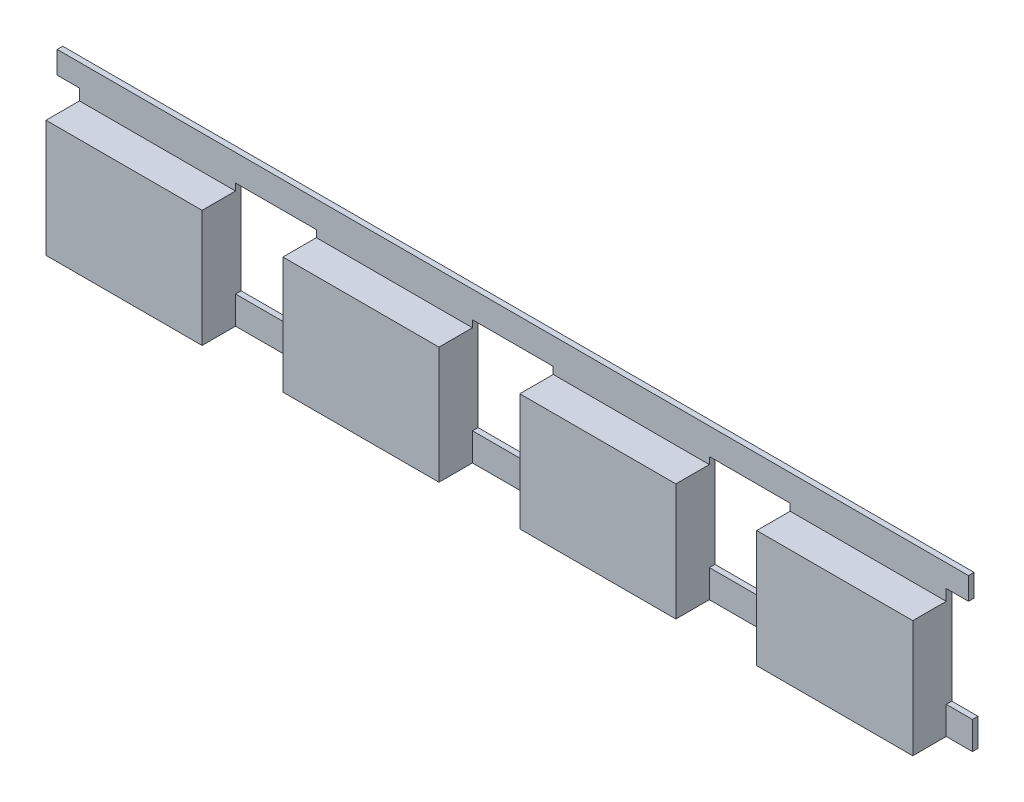
SolidWorks part; units mm, degrees
ref_plane "Спереди" through (0, 0, 0) normal (0, 0, 1) x (1, 0, 0)
ref_plane "Сверху" through (0, 0, 0) normal (0, 1, 0) x (1, 0, 0)
ref_plane "Справа" through (0, 0, 0) normal (1, 0, 0) x (0, 0, -1)
other "Configuration Table"
sketch "Эскиз1" plane through (0, 0, 0) normal (0, 0, 1) x (1, 0, 0)
  line L1 (-2.8, -2.1) -> (2.8, -2.1)
  line L2 (-2.8, -2.1) -> (-2.8, 2.1)
  line L3 (-2.8, 2.1) -> (2.8, 2.1)
  line L4 (2.8, -2.1) -> (2.8, 2.1)
  line L5 (-2.8, -2.1) -> (2.8, 2.1) construction
  line L6 (-2.8, 2.1) -> (2.8, -2.1) construction
  point P0 (0, 0)
  dimension "D1" = 4.2
  dimension "D2" = 5.6
extrude "Бобышка-Вытянуть1" add sketch "Эскиз1" along normal blind 1.4
sketch "Эскиз2" plane through (0, 0, 1.4) normal (0, 0, 1) x (1, 0, 0)
  line L0 (0, 0) -> (-1.0279, 0)
sketch "Эскиз3" plane through (0, 0, 0) normal (0, 0, -1) x (-1, 0, 0)
  line L1 (2.8, 2.1) -> (-28.3, 2.1)
  line L2 (2.8, 2.1) -> (2.8, 3.3)
  line L3 (2.8, 3.3) -> (-28.3, 3.3)
  line L4 (-28.3, 2.1) -> (-28.3, 3.3)
  line L5 (2.8, 2.1) -> (-28.3, 2.1)
  line L6 (2.8, 2.1) -> (2.8, 1.8)
  line L7 (2.8, 1.8) -> (-28.3, 1.8)
  line L8 (-28.3, 2.1) -> (-28.3, 1.8)
  line M5 (-2.8, 2.1) -> (-2.8, -2.1)
  line M7 (2.8, -2.1) -> (2.8, 2.1)
  line M8 (2.8, 2.1) -> (-2.8, 2.1)
  dimension "D1" = 1.2
  dimension "D2" = 0.3
  dimension "D3" = 31.1
  dimension "D4" = 31.1
extrude "Бобышка-Вытянуть2" add sketch "Эскиз3" against normal blind 0.2 contours L4 L1 L2 L3 M8 | L1 L8 L7 M5 | L7 M7 M8 M5 region at (0, 1.95, 0) region at (12.75, 2.7, 0) region at (15.55, 1.95, 0)
pattern_linear "Линейный массив1" count 4 spacing 8.5 along (1, 0, 0) of "Бобышка-Вытянуть1"
sketch "Эскиз4" plane through (0, 0, 0) normal (0, 0, -1) x (-1, 0, 0)
  line L0 (-22.7, 1.8) -> (-19.8, 1.8)
  line L2 (-22.7, 2.35) -> (-19.8, 2.35)
  line L3 (-22.7, 2.35) -> (-22.7, 1.25)
  line L4 (-22.7, 1.25) -> (-19.8, 1.25)
  line L5 (-19.8, 2.35) -> (-19.8, 1.25)
  line L6 (-22.7, 2.35) -> (-19.8, 1.25) construction
  line L7 (-22.7, 1.25) -> (-19.8, 2.35) construction
  line L8 (-14.2, 2.35) -> (-14.2, 1.25)
  line L9 (-14.2, 2.35) -> (-11.3, 2.35)
  line L10 (-11.3, 2.35) -> (-11.3, 1.25)
  line L11 (-14.2, 1.25) -> (-11.3, 1.25)
  line L12 (-5.7, 2.35) -> (-5.7, 1.25)
  line L13 (-5.7, 2.35) -> (-2.8, 2.35)
  line L14 (-2.8, 2.35) -> (-2.8, 1.25)
  line L15 (-5.7, 1.25) -> (-2.8, 1.25)
  point P4 (-21.25, 1.8)
  dimension "D1" = 1.1
  dimension "D2" = 3
extrude "Вырез-Вытянуть1" cut sketch "Эскиз4" against normal blind 0.2 contours L12 L15 L14 L13 | L8 L11 L10 L9 | L5 L0 L4 | L5 L2 L3 L0 region at (21.25, 2.075, 0) region at (21.25, 1.525, 0) region at (12.75, 1.8, 0) region at (4.25, 1.8, 0)
sketch "Эскиз5" plane through (28.3, 0, 0) normal (1, 0, 0) x (0, 0, -1)
  line L0 (0, -2.1) -> (0, 3.3) construction
  line L1 (-0.2, 3.3) -> (0, 3.3)
  line L2 (-0.2, 3.3) -> (-0.2, 2.5)
  line L3 (-0.2, 2.5) -> (0, 2.5)
  line L4 (0, 3.3) -> (0, 2.5)
  dimension "D1" = 0.8
extrude "Бобышка-Вытянуть3" add sketch "Эскиз5" along normal blind 0.8
sketch "Эскиз6" plane through (-2.8, 0, 0) normal (-1, 0, 0) x (0, 0, 1)
  line L0 (0.2, 2.1) -> (0.2, 3.3) construction
  line L1 (0, 3.3) -> (0.2, 3.3)
  line L2 (0, 3.3) -> (0, 2.5)
  line L3 (0, 2.5) -> (0.2, 2.5)
  line L4 (0.2, 3.3) -> (0.2, 2.5)
  dimension "D1" = 0.8
extrude "Бобышка-Вытянуть4" add sketch "Эскиз6" along normal blind 0.8
sketch "Эскиз7" plane through (0, 0, 0) normal (0, 0, -1) x (-1, 0, 0)
  line L1 (-29.2405, -2.1) -> (3.6437, -2.1)
  line L2 (-29.2405, -2.1) -> (-29.2405, -1.1)
  line L3 (-29.2405, -1.1) -> (3.6437, -1.1)
  line L4 (3.6437, -2.1) -> (3.6437, -1.1)
  dimension "D1" = 1
extrude "Бобышка-Вытянуть5" add sketch "Эскиз7" against normal blind 0.2
sketch "Эскиз8" plane through (0, 0, 1.4) normal (0, 0, 1) x (1, 0, 0)
  line L0 (28.3, -2.1) -> (28.3, 2.1) construction
  line L1 (28.3, 2.1) -> (22.7, 2.1) construction
  line L2 (22.7, 2.1) -> (22.7, -2.1) construction
  line L3 (22.7, -2.1) -> (28.3, -2.1) construction
  line L4 (19.8, -2.1) -> (19.8, 2.1) construction
  line L5 (19.8, 2.1) -> (14.2, 2.1) construction
  line L6 (14.2, 2.1) -> (14.2, -2.1) construction
  line L7 (14.2, -2.1) -> (19.8, -2.1) construction
  line L8 (11.3, -2.1) -> (11.3, 2.1) construction
  line L9 (11.3, 2.1) -> (5.7, 2.1) construction
  line L10 (5.7, 2.1) -> (5.7, -2.1) construction
  line L11 (5.7, -2.1) -> (11.3, -2.1) construction
  line L12 (2.8, -2.1) -> (2.8, 2.1) construction
  line L13 (2.8, 2.1) -> (-2.8, 2.1) construction
  line L14 (-2.8, 2.1) -> (-2.8, -2.1) construction
  line L15 (-2.8, -2.1) -> (2.8, -2.1) construction
  line L16 (28.3, -2.1) -> (28.3, 2.1)
  line L17 (28.3, 2.1) -> (22.7, 2.1)
  line L18 (22.7, 2.1) -> (22.7, -2.1)
  line L19 (22.7, -2.1) -> (28.3, -2.1)
  line L20 (19.8, -2.1) -> (19.8, 2.1)
  line L21 (19.8, 2.1) -> (14.2, 2.1)
  line L22 (14.2, 2.1) -> (14.2, -2.1)
  line L23 (14.2, -2.1) -> (19.8, -2.1)
  line L24 (11.3, -2.1) -> (11.3, 2.1)
  line L25 (11.3, 2.1) -> (5.7, 2.1)
  line L26 (5.7, 2.1) -> (5.7, -2.1)
  line L27 (5.7, -2.1) -> (11.3, -2.1)
  line L28 (2.8, -2.1) -> (2.8, 2.1)
  line L29 (2.8, 2.1) -> (-2.8, 2.1)
  line L30 (-2.8, 2.1) -> (-2.8, -2.1)
  line L31 (-2.8, -2.1) -> (2.8, -2.1)
  line L32 (11.9, -2.7) -> (11.9, 2.7)
  line L33 (11.9, 2.7) -> (5.1, 2.7)
  line L34 (5.1, 2.7) -> (5.1, -2.7)
  line L35 (5.1, -2.7) -> (11.9, -2.7)
  line L36 (20.4, -2.7) -> (20.4, 2.7)
  line L37 (20.4, 2.7) -> (13.6, 2.7)
  line L38 (13.6, 2.7) -> (13.6, -2.7)
  line L39 (13.6, -2.7) -> (20.4, -2.7)
  line L40 (28.9, -2.7) -> (28.9, 2.7)
  line L41 (28.9, 2.7) -> (22.1, 2.7)
  line L42 (22.1, 2.7) -> (22.1, -2.7)
  line L43 (22.1, -2.7) -> (28.9, -2.7)
  line L44 (3.4, -2.7) -> (3.4, 2.7)
  line L45 (3.4, 2.7) -> (-3.4, 2.7)
  line L46 (-3.4, 2.7) -> (-3.4, -2.7)
  line L47 (-3.4, -2.7) -> (3.4, -2.7)
  line L48 (2.2, -1.5) -> (2.2, 1.5)
  line L49 (2.2, 1.5) -> (-2.2, 1.5)
  line L50 (-2.2, 1.5) -> (-2.2, -1.5)
  line L51 (-2.2, -1.5) -> (2.2, -1.5)
  line L52 (10.7, -1.5) -> (10.7, 1.5)
  line L53 (10.7, 1.5) -> (6.3, 1.5)
  line L54 (6.3, 1.5) -> (6.3, -1.5)
  line L55 (6.3, -1.5) -> (10.7, -1.5)
  line L56 (19.2, -1.5) -> (19.2, 1.5)
  line L57 (19.2, 1.5) -> (14.8, 1.5)
  line L58 (14.8, 1.5) -> (14.8, -1.5)
  line L59 (14.8, -1.5) -> (19.2, -1.5)
  line L60 (27.7, -1.5) -> (27.7, 1.5)
  line L61 (27.7, 1.5) -> (23.3, 1.5)
  line L62 (23.3, 1.5) -> (23.3, -1.5)
  line L63 (23.3, -1.5) -> (27.7, -1.5)
  dimension "D1" = 0.6
  dimension "D2" = 0.6
extrude "Вырез-Вытянуть2" cut sketch "Эскиз8" against normal blind 1 from offset 0.4 contours L50 L51 L48 L49 | L54 L55 L52 L53 | L58 L59 L56 L57 | L62 L63 L60 L61 region at (0, 0, 1.4) region at (8.5, 0, 1.4) region at (17, 0, 1.4) region at (25.5, 0, 1.4) offset against normal yes
